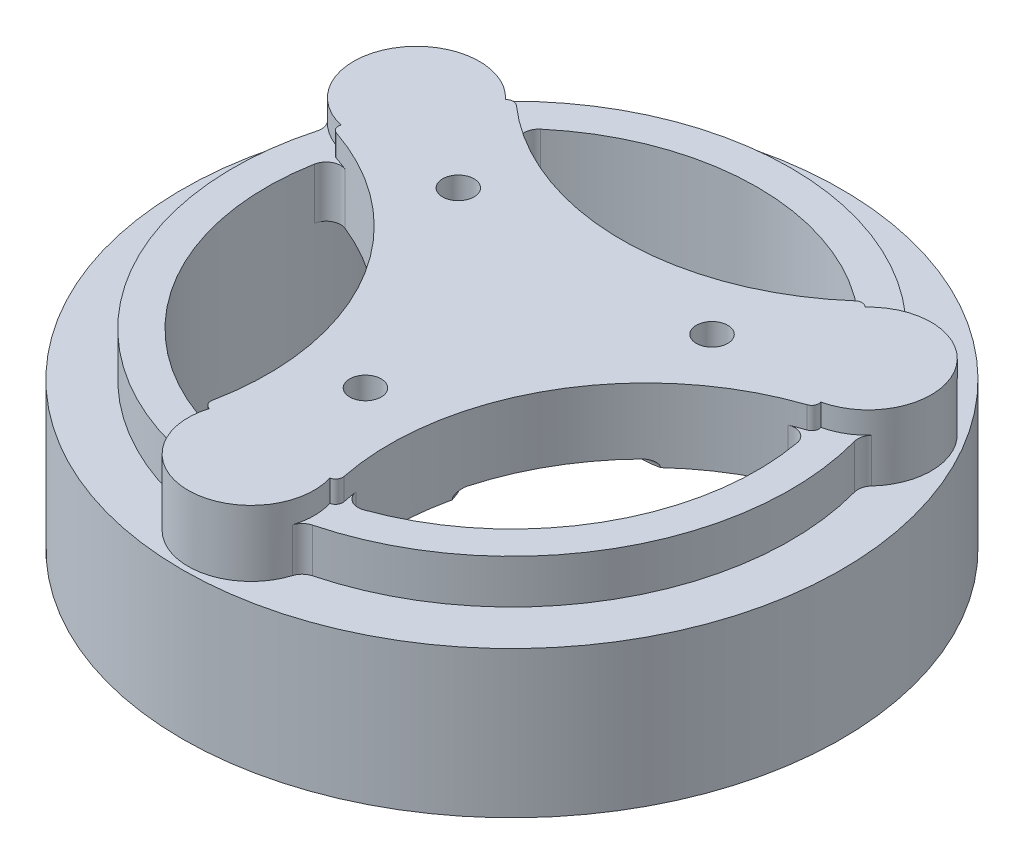
SolidWorks part; units mm, degrees
ref_plane "前视基准面" through (0, 0, 0) normal (0, 0, 1) x (1, 0, 0)
ref_plane "上视基准面" through (0, 0, 0) normal (0, 1, 0) x (1, 0, 0)
ref_plane "右视基准面" through (0, 0, 0) normal (1, 0, 0) x (0, 0, -1)
other "Configuration Table"
sketch "草图1" plane through (0, 0, 0) normal (0, 1, 0) x (1, 0, 0)
  circle A0 centre (0, 0) radius 45
  circle A1 centre (0, 0) radius 40 construction
  dimension "D1" = 90
  dimension "D2" = 80
extrude "凸台-拉伸2" add sketch "草图1" along normal blind 20 and the other way blind 0.01 contours A0
sketch "草图2" plane through (0, 20, 0) normal (0, 1, 0) x (1, 0, 0)
  circle A0 centre (0, 0) radius 33.5
  dimension "D1" = 67
extrude "切除-拉伸1" cut sketch "草图2" against normal up to next contours A0
sketch "草图6" plane through (0, 20, 0) normal (0, 1, 0) x (1, 0, 0)
  circle A0 centre (0, 0) radius 38.0586
  circle A1 centre (0, 0) radius 33.5 construction
  circle A2 centre (0, 0) radius 33.5
  dimension "D1" = 76.1171
extrude "凸台-拉伸3" add sketch "草图6" along normal blind 6
sketch "草图7" plane through (0, 26, 0) normal (0, 1, 0) x (1, 0, 0)
  arc A0 (-13.2818, -42.9953) -> (-43.8759, 9.9953) centre (-43.3013, -25) ccw
  arc A1 (-30.5941, 33) -> (30.5941, 33) centre (0, 50) ccw
  arc A2 (43.8759, 9.9953) -> (13.2818, -42.9953) centre (43.3013, -25) ccw
  arc A3 (-13.2818, -42.9953) -> (13.2818, -42.9953) centre (0, 0) ccw
  arc A4 (-30.5941, 33) -> (-43.8759, 9.9953) centre (0, 0) ccw
  arc A5 (43.8759, 9.9953) -> (30.5941, 33) centre (0, 0) ccw
  point P9 (0, 0)
  dimension "D3" = 70
  dimension "D4" = 90
  dimension "D2" = 50
  dimension "D1" = 3
extrude "凸台-拉伸5" add sketch "草图7" along normal mid plane 12 contours A0 A4 A1 A5 A2 A3
sketch "草图18" plane through (0, 32, 0) normal (0, 1, 0) x (1, 0, 0)
  arc A6 (-13.2818, -42.9953) -> (13.2818, -42.9953) centre (0, 0) ccw
  arc A7 (43.8759, 9.9953) -> (13.2818, -42.9953) centre (43.3013, -25) ccw
  arc A8 (43.8759, 9.9953) -> (30.5941, 33) centre (0, 0) ccw
  arc A9 (-30.5941, 33) -> (30.5941, 33) centre (0, 50) ccw
  arc A10 (-30.5941, 33) -> (-43.8759, 9.9953) centre (0, 0) ccw
  arc A11 (-13.2818, -42.9953) -> (-43.8759, 9.9953) centre (-43.3013, -25) ccw
  arc A12 (-13.2818, -42.9953) -> (13.2818, -42.9953) centre (0, 0) ccw
  arc A13 (43.8759, 9.9953) -> (13.2818, -42.9953) centre (43.3013, -25) ccw
  arc A14 (43.8759, 9.9953) -> (30.5941, 33) centre (0, 0) ccw
  arc A15 (-30.5941, 33) -> (30.5941, 33) centre (0, 50) ccw
  arc A16 (-30.5941, 33) -> (-43.8759, 9.9953) centre (0, 0) ccw
  arc A17 (-13.2818, -42.9953) -> (-43.8759, 9.9953) centre (-43.3013, -25) ccw
  dimension "D1" = 0
extrude "切除-拉伸2" cut sketch "草图18" against normal blind 3
sketch "草图19" plane through (0, 29, 0) normal (0, 1, 0) x (1, 0, 0)
  line L0 (-43.3013, -25) -> (0, 0) construction
  line L1 (0, 0) -> (17.3205, 10) construction
  circle A0 centre (-17.3205, 10) radius 2.15
  circle A1 centre (17.3205, 10) radius 2.15
  circle A2 centre (0, -20) radius 2.15
  arc A3 (-13.2818, -42.9953) -> (-43.8759, 9.9953) centre (-43.3013, -25) ccw construction
  arc A4 (-13.2818, -42.9953) -> (-43.8759, 9.9953) centre (-43.3013, -25) ccw
  point P9 (0, 0)
  dimension "D2" = 4.3
  dimension "D3" = 20
  dimension "D1" = 3
extrude "切除-拉伸3" cut sketch "草图19" along normal mid plane 10 contours A0 | A1 | A2 region at (-17.3205, 29, -10) region at (17.3205, 29, -10)
sketch "草图20" plane through (0, 29, 0) normal (0, 1, 0) x (1, 0, 0)
  circle A0 centre (0, -20) radius 2.15 construction
  circle A1 centre (17.3205, 10) radius 2.15 construction
  circle A2 centre (-17.3205, 10) radius 2.15 construction
  circle A3 centre (0, -20) radius 2.15 construction
  circle A4 centre (17.3205, 10) radius 2.15 construction
  circle A5 centre (-17.3205, 10) radius 2.15 construction
  arc A6 (-13.2818, -42.9953) -> (-43.8759, 9.9953) centre (-43.3013, -25) ccw
  arc A7 (-13.2818, -42.9953) -> (13.2818, -42.9953) centre (0, 0) ccw
  arc A8 (43.8759, 9.9953) -> (13.2818, -42.9953) centre (43.3013, -25) ccw
  arc A9 (43.8759, 9.9953) -> (30.5941, 33) centre (0, 0) ccw
  arc A10 (-30.5941, 33) -> (30.5941, 33) centre (0, 50) ccw
  arc A11 (-30.5941, 33) -> (-43.8759, 9.9953) centre (0, 0) ccw
  arc A12 (-9.2788, -33.2143) -> (-9.1574, -17.306) centre (-43.3013, -25) ccw
  arc A13 (-13.2818, -42.9953) -> (13.2818, -42.9953) centre (0, 0) ccw construction
  arc A14 (33.4038, 8.5714) -> (19.5662, 0.7225) centre (43.3013, -25) ccw
  arc A15 (43.8759, 9.9953) -> (30.5941, 33) centre (0, 0) ccw construction
  arc A16 (-24.125, 24.6429) -> (-10.4088, 16.5836) centre (0, 50) ccw
  arc A17 (-30.5941, 33) -> (-43.8759, 9.9953) centre (0, 0) ccw construction
  arc A18 (-24.125, 24.6429) -> (-33.4038, 8.5714) centre (-30.7045, 17.7273) ccw
  arc A19 (-9.2788, -33.2143) -> (9.2788, -33.2143) centre (0, -35.4545) ccw
  arc A20 (33.4038, 8.5714) -> (24.125, 24.6429) centre (30.7045, 17.7273) ccw
  arc A21 (-10.4088, 16.5836) -> (-19.5662, 0.7225) centre (-17.3205, 10) cw
  arc A22 (19.5662, 0.7225) -> (10.4088, 16.5836) centre (17.3205, 10) cw
  arc A23 (-9.1574, -17.306) -> (9.1574, -17.306) centre (0, -20) cw
  arc A24 (10.4088, 16.5836) -> (24.125, 24.6429) centre (0, 50) ccw
  arc A25 (-19.5662, 0.7225) -> (-33.4038, 8.5714) centre (-43.3013, -25) ccw
  arc A26 (9.1574, -17.306) -> (9.2788, -33.2143) centre (43.3013, -25) ccw
  circle A27 centre (0, 0) radius 45 construction
  circle A28 centre (0, 0) radius 45 construction
  arc A29 (43.8759, 9.9953) -> (13.2818, -42.9953) centre (43.3013, -25) ccw construction
  arc A30 (-30.5941, 33) -> (30.5941, 33) centre (0, 50) ccw construction
  arc A39 (-13.2818, -42.9953) -> (-43.8759, 9.9953) centre (-43.3013, -25) ccw construction
  arc A40 (33.4038, 8.5714) -> (9.2788, -33.2143) centre (43.3013, -25) ccw
  arc A41 (-24.125, 24.6429) -> (24.125, 24.6429) centre (0, 50) ccw
  arc A42 (-9.2788, -33.2143) -> (-33.4038, 8.5714) centre (-43.3013, -25) ccw
  point P33 (0, 0)
  point P42 (0, 0)
  circle M13 centre (-17.3205, 10) radius 2.15
  circle M14 centre (17.3205, 10) radius 2.15
  circle M15 centre (0, -20) radius 2.15
  arc M16 (-43.8759, 9.9953) -> (-13.2818, -42.9953) centre (-43.3013, -25) cw
  arc M18 (13.2818, -42.9953) -> (43.8759, 9.9953) centre (43.3013, -25) cw
  arc M20 (30.5941, 33) -> (-30.5941, 33) centre (0, 50) cw
  dimension "D2" = 3
  dimension "D3" = 35
  dimension "D4" = 43.589
  dimension "D5" = 3
  dimension "D1" = 0
extrude "凸台-拉伸6" add sketch "草图20" against normal blind 10 contours A21 A18 M20 M16 M13 | A22 A20 M18 M20 M14 | A23 A19 M16 M18 M15 region at (0, 29, 28.0659) region at (-24.3058, 29, -14.0329) region at (24.3058, 29, -14.0329)
sketch "草图22" plane through (0, 29, 0) normal (0, 1, 0) x (1, 0, 0)
  line L0 (-30.8398, 17.8054) -> (-17.3205, 10) construction
  line L1 (-17.3205, 10) -> (0, 0) construction
  line L2 (-23.8617, 24.395) -> (-24.5435, 23.6634)
  line L3 (-33.0575, 8.4674) -> (-32.7649, 9.4236)
  line L4 (33.0575, 8.4674) -> (32.7649, 9.4236)
  line L5 (23.8617, 24.395) -> (24.5435, 23.6634)
  line L6 (-9.1958, -32.8624) -> (-8.2214, -33.087)
  line L7 (9.1958, -32.8624) -> (8.2214, -33.087)
  circle A0 centre (0, 0) radius 45 construction
  arc A1 (-13.2818, -42.9953) -> (13.2818, -42.9953) centre (0, 0) ccw
  arc A2 (-24.5435, 23.6634) -> (-32.7649, 9.4236) centre (-30.8398, 17.8054) ccw
  arc A3 (32.7649, 9.4236) -> (24.5435, 23.6634) centre (30.8398, 17.8054) ccw
  circle A4 centre (-17.3205, 10) radius 2.15
  circle A5 centre (-17.3205, 10) radius 2.15 construction
  arc A6 (43.8759, 9.9953) -> (13.2818, -42.9953) centre (43.3013, -25) ccw
  arc A7 (43.8759, 9.9953) -> (30.5941, 33) centre (0, 0) ccw
  arc A8 (-30.5941, 33) -> (30.5941, 33) centre (0, 50) ccw
  arc A9 (-30.5941, 33) -> (-43.8759, 9.9953) centre (0, 0) ccw
  arc A10 (-13.2818, -42.9953) -> (-43.8759, 9.9953) centre (-43.3013, -25) ccw
  arc A11 (-13.2818, -42.9953) -> (13.2818, -42.9953) centre (0, 0) ccw
  arc A12 (43.8759, 9.9953) -> (33.0575, 8.4674) centre (43.3013, -25) ccw
  arc A13 (43.8759, 9.9953) -> (30.5941, 33) centre (0, 0) ccw
  arc A14 (-30.5941, 33) -> (-23.8617, 24.395) centre (0, 50) ccw
  arc A15 (-30.5941, 33) -> (-43.8759, 9.9953) centre (0, 0) ccw
  arc A16 (-13.2818, -42.9953) -> (-9.1958, -32.8624) centre (-43.3013, -25) ccw
  arc A17 (-13.2818, -42.9953) -> (13.2818, -42.9953) centre (0, 0) ccw
  arc A18 (-8.2214, -33.087) -> (8.2214, -33.087) centre (0, -35.6108) ccw
  arc A19 (23.8617, 24.395) -> (30.5941, 33) centre (0, 50) ccw
  arc A20 (-30.5941, 33) -> (-43.8759, 9.9953) centre (0, 0) ccw
  arc A21 (43.8759, 9.9953) -> (30.5941, 33) centre (0, 0) ccw
  arc A22 (9.1958, -32.8624) -> (13.2818, -42.9953) centre (43.3013, -25) ccw
  arc A23 (-33.0575, 8.4674) -> (-43.8759, 9.9953) centre (-43.3013, -25) ccw
  arc A26 (-13.2818, -42.9953) -> (-43.8759, 9.9953) centre (-43.3013, -25) ccw construction
  point P15 (0, 0)
  point P18 (0, 0)
  point P27 (0, 0)
  point P28 (14.921, 18.3399)
  point P29 (24.5435, 4.6263)
  point P30 (0, 0)
  point P42 (0, 0)
  point P43 (8.4377, -28.0873)
  point P44 (-32.7649, 8.4674)
  point P47 (-8.4377, -28.0873)
  point P48 (-8.3013, -25)
  arc M14 (13.2818, -42.9953) -> (43.8759, 9.9953) centre (43.3013, -25) cw
  arc M15 (43.8759, 9.9953) -> (30.5941, 33) centre (0, 0) ccw
  arc M16 (30.5941, 33) -> (-30.5941, 33) centre (0, 50) cw
  arc M17 (-30.5941, 33) -> (-43.8759, 9.9953) centre (0, 0) ccw
  arc M18 (-43.8759, 9.9953) -> (-13.2818, -42.9953) centre (-43.3013, -25) cw
  arc M19 (-13.2818, -42.9953) -> (13.2818, -42.9953) centre (0, 0) ccw
  dimension "D2" = 0
  dimension "D3" = 1
  dimension "D4" = 8.6
  dimension "D5" = 35.6108
  dimension "D1" = 0
  dimension "D6" = 3
extrude "切除-拉伸4" cut sketch "草图22" against normal up to surface (3 mm away) contours A2 L2 L3 M16 M17 M18 | A3 L4 L5 M14 M15 M16 | A18 L6 L7 M18 M19 M14 region at (-24.4343, 29, -24.245) region at (27.8151, 29, -28.2381) region at (-8.7742, 29, 33.2593) up to face at (26.5571, 26, 15.3327)
sketch "草图23" plane through (0, 26, 0) normal (0, 1, 0) x (1, 0, 0)
  line L6 (-23.8617, 24.395) -> (-24.5435, 23.6634)
  line L7 (-32.7649, 9.4236) -> (-33.0575, 8.4674)
  line L8 (-9.1958, -32.8624) -> (-8.2214, -33.087)
  line L9 (8.2214, -33.087) -> (9.1958, -32.8624)
  line L10 (33.0575, 8.4674) -> (32.7649, 9.4236)
  line L11 (24.5435, 23.6634) -> (23.8617, 24.395)
  circle A0 centre (0, 0) radius 45 construction
  arc A1 (-30.5941, 33) -> (-43.8759, 9.9953) centre (0, 0) ccw
  arc A2 (-26.5845, 27.2345) -> (-27.8985, 25.8868) centre (0, 0) ccw
  arc A3 (27.8985, 25.8868) -> (26.5845, 27.2345) centre (0, 0) ccw
  arc A4 (36.878, 9.4056) -> (36.3679, 11.2175) centre (0, 0) ccw
  arc A5 (43.8759, 9.9953) -> (30.5941, 33) centre (0, 0) ccw
  arc A6 (-10.2936, -36.6401) -> (-8.4693, -37.1042) centre (0, 0) ccw
  arc A7 (-36.3679, 11.2175) -> (-36.878, 9.4056) centre (0, 0) ccw
  arc A8 (-13.2818, -42.9953) -> (13.2818, -42.9953) centre (0, 0) ccw
  arc A9 (8.4693, -37.1042) -> (10.2936, -36.6401) centre (0, 0) ccw
  arc A12 (10.2936, -36.6401) -> (36.878, 9.4056) centre (0, 0) ccw
  arc A13 (43.8759, 9.9953) -> (36.878, 9.4056) centre (43.3013, -25) ccw
  arc A14 (43.8759, 9.9953) -> (30.5941, 33) centre (0, 0) ccw
  arc A15 (26.5845, 27.2345) -> (30.5941, 33) centre (0, 50) ccw
  arc A16 (26.5845, 27.2345) -> (-26.5845, 27.2345) centre (0, 0) ccw
  arc A17 (-30.5941, 33) -> (-26.5845, 27.2345) centre (0, 50) ccw
  arc A18 (-30.5941, 33) -> (-43.8759, 9.9953) centre (0, 0) ccw
  arc A19 (-36.878, 9.4056) -> (-43.8759, 9.9953) centre (-43.3013, -25) ccw
  arc A20 (-36.878, 9.4056) -> (-10.2936, -36.6401) centre (0, 0) ccw
  arc A21 (-13.2818, -42.9953) -> (-10.2936, -36.6401) centre (-43.3013, -25) ccw
  arc A22 (-13.2818, -42.9953) -> (13.2818, -42.9953) centre (0, 0) ccw
  arc A23 (10.2936, -36.6401) -> (13.2818, -42.9953) centre (43.3013, -25) ccw
  arc A25 (43.8759, 9.9953) -> (36.878, 9.4056) centre (43.3013, -25) ccw
  arc A26 (43.8759, 9.9953) -> (30.5941, 33) centre (0, 0) ccw
  arc A27 (26.5845, 27.2345) -> (30.5941, 33) centre (0, 50) ccw
  arc A29 (-30.5941, 33) -> (-26.5845, 27.2345) centre (0, 50) ccw
  arc A30 (-30.5941, 33) -> (-43.8759, 9.9953) centre (0, 0) ccw
  arc A31 (-36.878, 9.4056) -> (-43.8759, 9.9953) centre (-43.3013, -25) ccw
  arc A33 (-13.2818, -42.9953) -> (-10.2936, -36.6401) centre (-43.3013, -25) ccw
  arc A34 (-13.2818, -42.9953) -> (13.2818, -42.9953) centre (0, 0) ccw
  arc A35 (10.2936, -36.6401) -> (13.2818, -42.9953) centre (43.3013, -25) ccw
  arc A38 (-23.8617, 24.395) -> (23.8617, 24.395) centre (0, 50) ccw
  arc A39 (-24.5435, 23.6634) -> (-32.7649, 9.4236) centre (-30.8398, 17.8054) ccw
  arc A40 (-9.1958, -32.8624) -> (-33.0575, 8.4674) centre (-43.3013, -25) ccw
  arc A41 (-8.2214, -33.087) -> (8.2214, -33.087) centre (0, -35.6108) ccw
  arc A42 (33.0575, 8.4674) -> (9.1958, -32.8624) centre (43.3013, -25) ccw
  arc A43 (32.7649, 9.4236) -> (24.5435, 23.6634) centre (30.8398, 17.8054) ccw
  arc A45 (-27.8985, 25.8868) -> (-36.3679, 11.2175) centre (-30.8398, 17.8054) ccw
  arc A47 (-8.4693, -37.1042) -> (8.4693, -37.1042) centre (0, -35.6108) ccw
  arc A49 (36.3679, 11.2175) -> (27.8985, 25.8868) centre (30.8398, 17.8054) ccw
  arc M32 (8.2214, -33.087) -> (-8.2214, -33.087) centre (0, -35.6108) cw
  arc M38 (-32.7649, 9.4236) -> (-24.5435, 23.6634) centre (-30.8398, 17.8054) cw
  arc M44 (24.5435, 23.6634) -> (32.7649, 9.4236) centre (30.8398, 17.8054) cw
  arc M46 (36.878, 9.4056) -> (43.8759, 9.9953) centre (43.3013, -25) cw
  arc M47 (43.8759, 9.9953) -> (30.5941, 33) centre (0, 0) ccw
  arc M48 (30.5941, 33) -> (26.5845, 27.2345) centre (0, 50) cw
  arc M50 (-26.5845, 27.2345) -> (-30.5941, 33) centre (0, 50) cw
  arc M51 (-30.5941, 33) -> (-43.8759, 9.9953) centre (0, 0) ccw
  arc M52 (-43.8759, 9.9953) -> (-36.878, 9.4056) centre (-43.3013, -25) cw
  arc M54 (-10.2936, -36.6401) -> (-13.2818, -42.9953) centre (-43.3013, -25) cw
  arc M55 (-13.2818, -42.9953) -> (13.2818, -42.9953) centre (0, 0) ccw
  arc M56 (13.2818, -42.9953) -> (10.2936, -36.6401) centre (43.3013, -25) cw
  dimension "D2" = 0
  dimension "D1" = 0
extrude "切除-拉伸5" cut sketch "草图23" against normal up to surface (6 mm away) contours A7 A2 M38 M50 M51 M52 | A4 A3 M46 M47 M48 M44 | A9 A6 M32 M54 M55 M56 region at (-38.541, 26, -22.2516) region at (27.4593, 26, -26.773) region at (-9.453, 26, 37.1533) up to face at (30.9802, 20, 17.8864)
fillet "圆角1" radius 2 6 edges at (-8.4693, 23, 37.1042) (-27.8985, 23, -25.8868) (36.3679, 23, -11.2175) (-36.3679, 23, -11.2175) (27.8985, 23, -25.8868) (8.4693, 23, 37.1042)
fillet "圆角2" radius 2 6 edges at (-32.4609, 22.5, -8.2789) (-9.0607, 22.5, 32.2514) (9.0607, 22.5, 32.2514) (32.4609, 22.5, -8.2789) (23.4002, 22.5, -23.9725) (-23.4002, 22.5, -23.9725)
fillet "圆角6" radius 1 6 edges at (9.1958, 27.5, 32.8624) (33.0575, 27.5, -8.4674) (23.8617, 27.5, -24.395) (-23.8617, 27.5, -24.395) (-33.0575, 27.5, -8.4674) (-9.1958, 27.5, 32.8624)
fillet "圆角8" radius 1 3 edges at (-9.0539, 20, -5.2273) (0, 20, 10.4545) (9.0539, 20, -5.2273)
sketch "草图24" plane through (0, 29, 0) normal (0, 1, 0) x (1, 0, 0)
  circle A0 centre (17.3205, 10) radius 2.15 construction
  circle A1 centre (0, -20) radius 2.15
  circle A2 centre (0, -20) radius 2.15
  circle A3 centre (-17.3205, 10) radius 2.15 construction
  circle A4 centre (17.3205, 10) radius 2.15
  circle A5 centre (-17.3205, 10) radius 2.15
  dimension "D1" = 0
extrude "切除-拉伸6" cut sketch "草图24" against normal up to surface (10 mm away) up to face at (17.3205, 19, -7.85)
